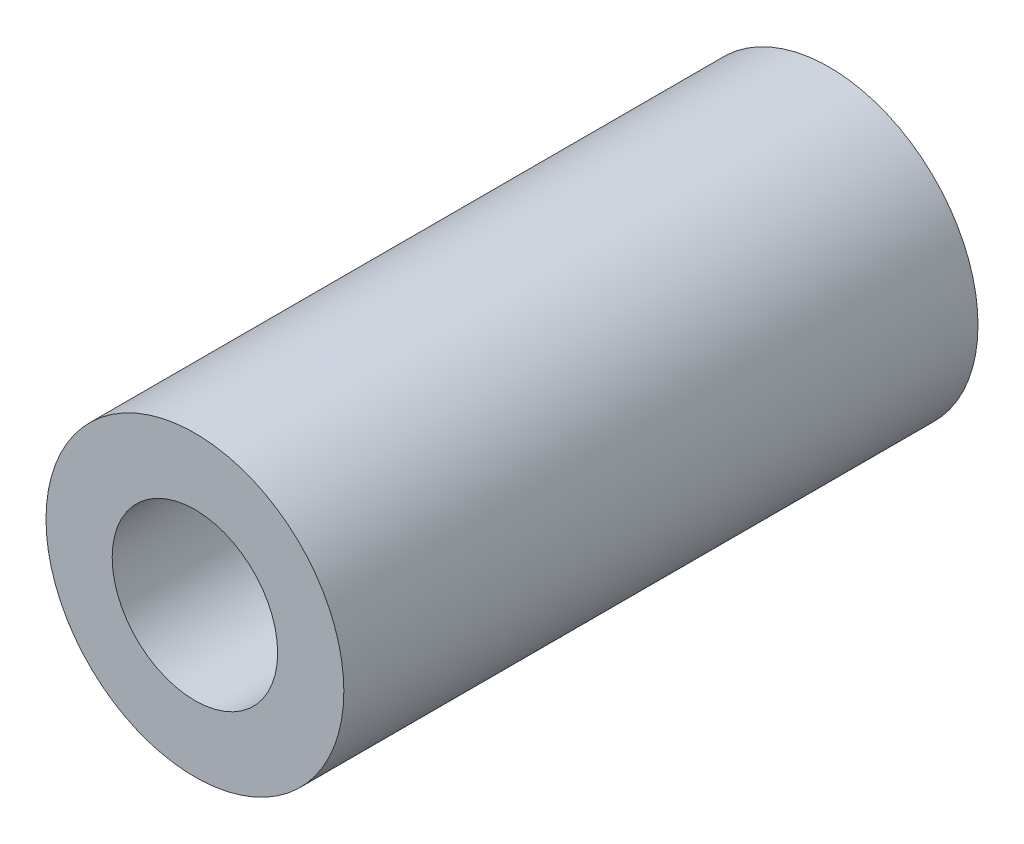
SolidWorks part; units mm, degrees
ref_plane "Front" through (0, 0, 0) normal (0, 0, 1) x (1, 0, 0)
ref_plane "Top" through (0, 0, 0) normal (0, 1, 0) x (1, 0, 0)
ref_plane "Right" through (0, 0, 0) normal (1, 0, 0) x (0, 0, -1)
sketch "Sketch1" plane through (0, 0, 0) normal (0, 0, 1) x (1, 0, 0)
  circle A0 centre (0, 0) radius 2.5
  circle A1 centre (0, 0) radius 4.5
extrude "Extrude1" add sketch "Sketch1" along normal blind 19.163
